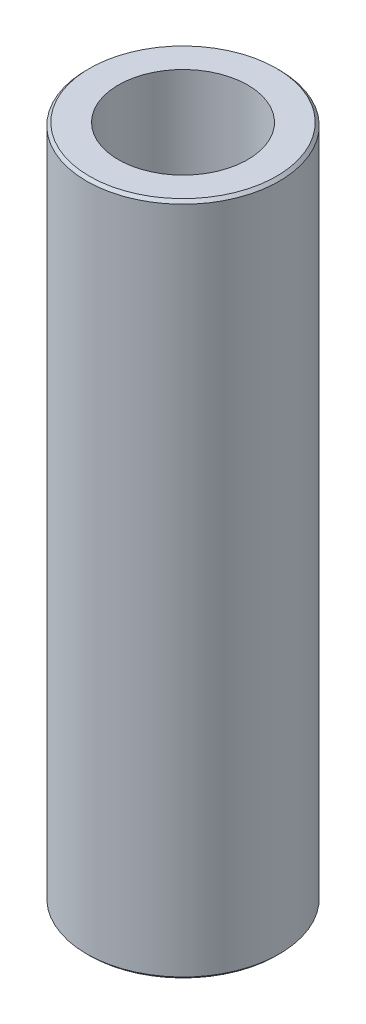
SolidWorks part; units mm, degrees
ref_plane "Front Plane" through (0, 0, 0) normal (0, 0, 1) x (1, 0, 0)
ref_plane "Top Plane" through (0, 0, 0) normal (0, 1, 0) x (1, 0, 0)
ref_plane "Right Plane" through (0, 0, 0) normal (1, 0, 0) x (0, 0, -1)
sketch "Sketch1" plane through (0, 0, 0) normal (0, 1, 0) x (1, 0, 0)
  circle A0 centre (0, 0) radius 35
  dimension "SHAFT_OD" = 70
extrude "Boss-Extrude1" add sketch "Sketch1" along normal blind 245.1949
sketch "Sketch2" plane through (0, 0, 0) normal (0, 1, 0) x (1, 0, 0)
  circle A0 centre (0, 0) radius 23.5099
  dimension "BORE_D" = 47.0197
extrude "Cut-Extrude1" cut sketch "Sketch2" along normal through all
chamfer "Chamfer1" distance 1.0324 angle 45 2 edges at (0, 245.1949, 35) (0, 0, 35)
